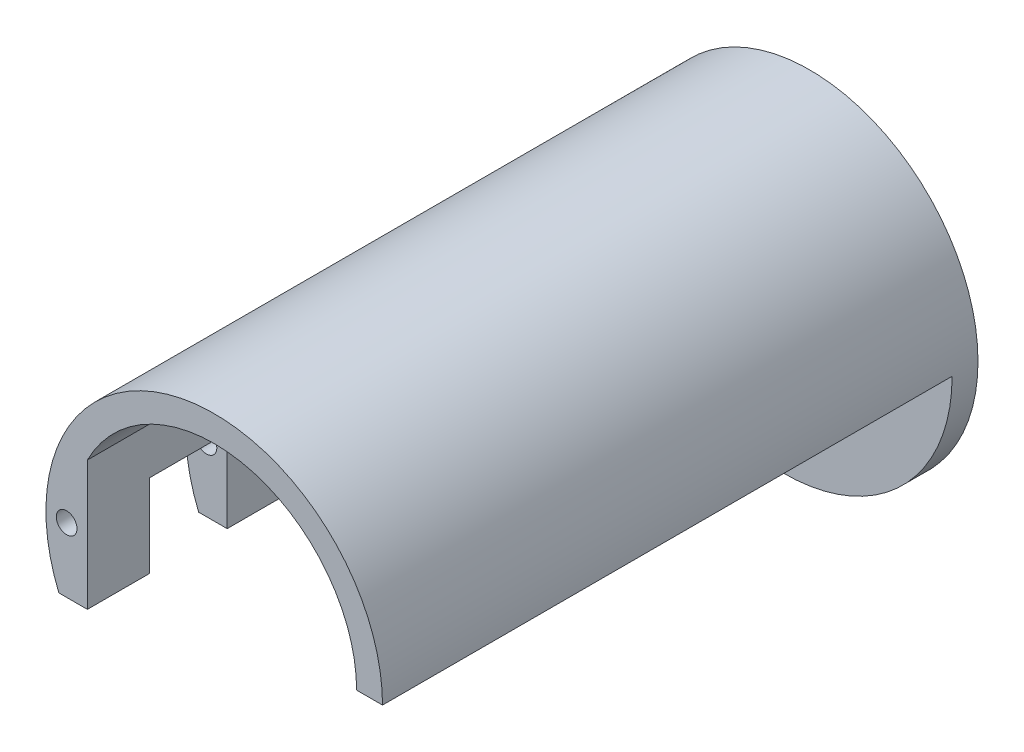
SolidWorks part; units mm, degrees
ref_plane "Alzado" through (0, 0, 0) normal (0, 0, 1) x (1, 0, 0)
ref_plane "Planta" through (0, 0, 0) normal (0, 1, 0) x (1, 0, 0)
ref_plane "Vista lateral" through (0, 0, 0) normal (1, 0, 0) x (0, 0, -1)
sketch "Croquis1" plane through (0, 0, 0) normal (0, 0, 1) x (1, 0, 0)
  circle A0 centre (0, 0) radius 32.5
  dimension "D1" = 65
extrude "Base" add sketch "Croquis1" along normal blind 5
sketch "Croquis2" plane through (0, 0, 5) normal (0, 0, 1) x (1, 0, 0)
  line L0 (0, 0) -> (0, 12.1765) construction
  line L1 (-24.5, 0) -> (-32.5, 0) construction
  line L2 (-24.5, 0) -> (-24.5, 12.49)
  line L3 (32.5, 0) -> (27.5, 0)
  line L4 (27.5, 0) -> (-24.5, 0) construction
  line L5 (-24.5, 0) -> (-24.5, -12.49)
  line L6 (-24.5, -12.49) -> (-30.0042, -12.49)
  circle A0 centre (0, 0) radius 32.5 construction
  arc A1 (32.5, 0) -> (-32.5, 0) centre (0, 0) ccw
  arc A2 (24.5, 12.49) -> (-24.5, 12.49) centre (0, 0) ccw construction
  arc A3 (24.5, 12.49) -> (-24.5, 12.49) centre (0, 0) ccw
  arc A4 (32.5, 0) -> (-30.0042, -12.49) centre (0, 0) ccw
  circle A5 centre (-28.5, 0) radius 2
  arc A6 (32.5, 0) -> (-30.0042, -12.49) centre (0, 0) ccw
  arc A7 (27.5, 0) -> (-27.4474, -1.7006) centre (0, 0) ccw
  arc A8 (27.5, 0) -> (-24.5, 12.49) centre (0, 0) ccw
  point P2 (0, 0)
  circle M1 centre (0, 0) radius 32.5
  dimension "D1" = 5
  dimension "D4" = 4
  dimension "D2" = 8
  dimension "D3" = 12.49
extrude "ParedFija" add sketch "Croquis2" along normal blind 110 contours A3 L3 L6 L5 L2 A5 M1 region at (-25.2905, -6.245, 5)
sketch "Croquis3" plane through (-24.5, 0, 0) normal (1, 0, 0) x (0, 0, -1)
  line L0 (-103, -12.49) -> (-103, 3.51)
  line L1 (-115, -12.49) -> (-5, -12.49) construction
  line L2 (-103, 3.51) -> (-88, 3.51)
  line L3 (-88, 3.51) -> (-88, -12.49)
  line L4 (-115, -12.49) -> (-5, -12.49) construction
  line L5 (-60, -12.49) -> (-60, 8) construction
  line L6 (-103, -12.49) -> (-88, -12.49)
  line L7 (-17, -12.49) -> (-32, -12.49)
  line L8 (-32, 3.51) -> (-32, -12.49)
  line L9 (-17, 3.51) -> (-32, 3.51)
  line L10 (-17, -12.49) -> (-17, 3.51)
  dimension "D1" = 16
  dimension "D2" = 15
  dimension "D3" = 12
extrude "HuecoVisagra" cut sketch "Croquis3" against normal up to next
